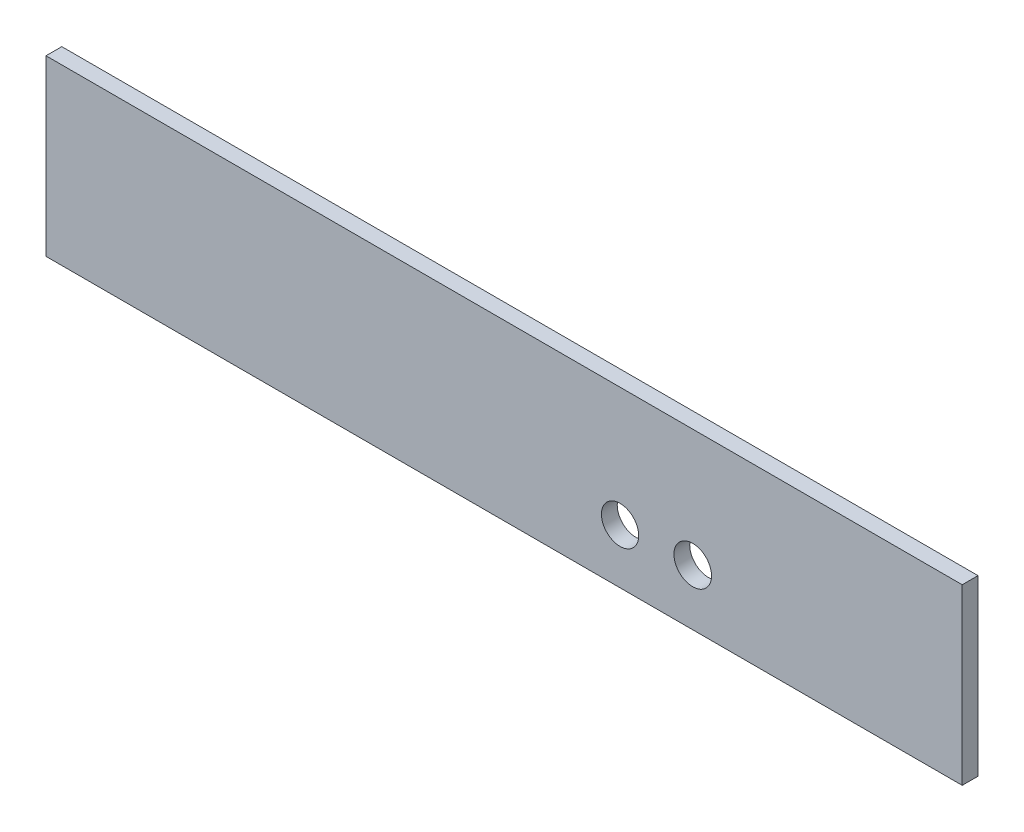
SolidWorks part; units mm, degrees
ref_plane "Plan de face" through (0, 0, 0) normal (0, 0, 1) x (1, 0, 0)
ref_plane "Plan de dessus" through (0, 0, 0) normal (0, 1, 0) x (1, 0, 0)
ref_plane "Plan de droite" through (0, 0, 0) normal (1, 0, 0) x (0, 0, -1)
sketch "Esquisse1" plane through (0, 0, 0) normal (0, 0, 1) x (1, 0, 0)
  line L1 (0, 0) -> (580, 0)
  line L2 (0, 0) -> (0, 110)
  line L3 (0, 110) -> (580, 110)
  line L4 (580, 0) -> (580, 110)
  dimension "D1" = 580
  dimension "D2" = 110
extrude "Boss.-Extru.1" add sketch "Esquisse1" along normal blind 10
sketch "Esquisse2" plane through (0, 0, 0) normal (0, 0, -1) x (-1, 0, 0)
  circle A0 centre (-363.4094, 34.5) radius 11.8
  circle A1 centre (-409.4094, 35.5) radius 11.9
extrude "Enlèv. mat.-Extru.1" cut sketch "Esquisse2" against normal blind 10
